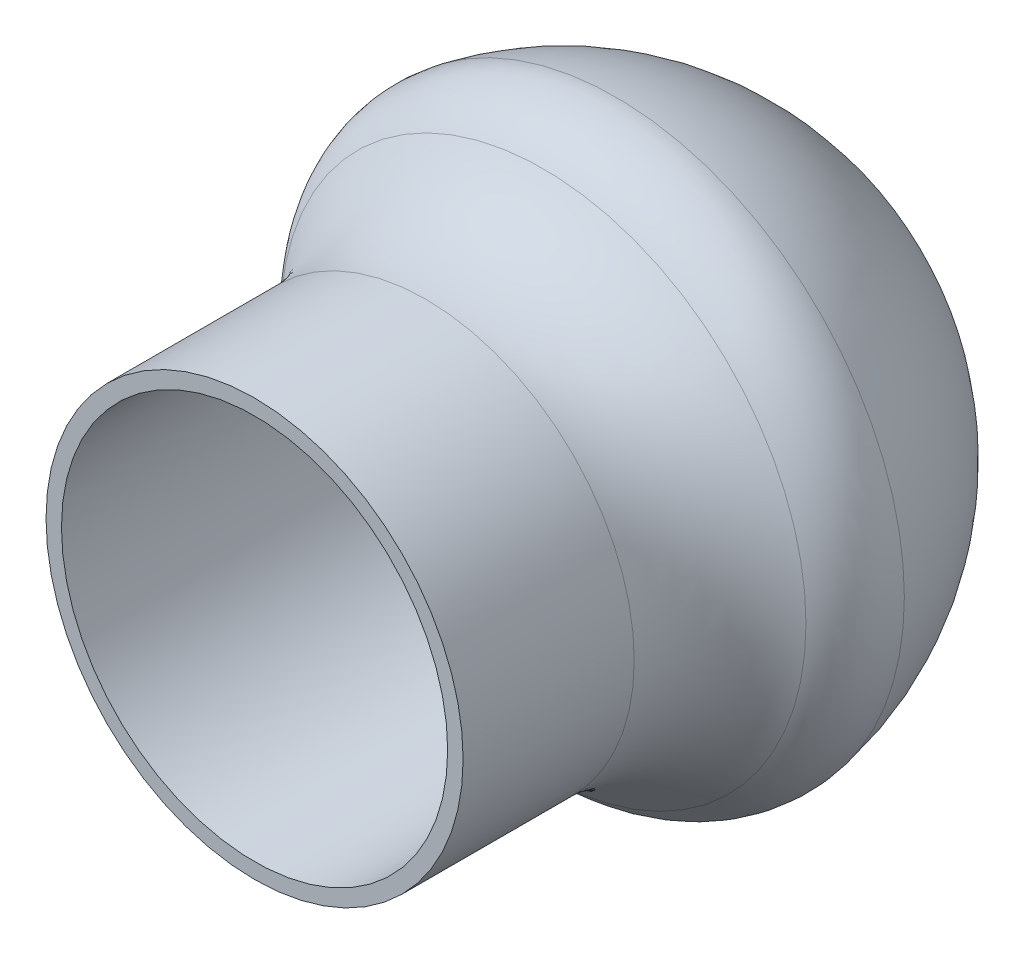
SolidWorks part; units mm, degrees
ref_plane "Plan de face" through (0, 0, 0) normal (0, 0, 1) x (1, 0, 0)
ref_plane "Plan de dessus" through (0, 0, 0) normal (0, 1, 0) x (1, 0, 0)
ref_plane "Plan de droite" through (0, 0, 0) normal (1, 0, 0) x (0, 0, -1)
sketch "Esquisse1" plane through (0, 0, 0) normal (0, 0, 1) x (1, 0, 0)
  circle A0 centre (0, 0) radius 12.5
  circle A1 centre (0, 0) radius 13.5
  dimension "D1" = 25
  dimension "D2" = 27
extrude "Boss.-Extru.1" add sketch "Esquisse1" along normal blind 20
sketch "Esquisse2" plane through (0, 0, 0) normal (1, 0, 0) x (0, 0, -1)
  line L0 (18.9865, 0) -> (0, 0)
  line L1 (0, 0) -> (0, -18.9865)
  arc A0 (0, -18.9865) -> (18.9865, 0) centre (0, 0) ccw
revolve "Révolution1" add sketch "Esquisse2" angle 360 about L0
fillet "Congé1" radius 10 1 edges at (-13.5, 0, 0)
fillet "Congé2" radius 5 1 edges at (-18.9865, 0, 0)
equation "\"diam_int\"=25"
equation "\"D1@Esquisse1\"=\"diam_int\""
equation "\"diam_ext\"= \"diam_int\" + 2"
equation "\"D2@Esquisse1\"=\"diam_ext\""
